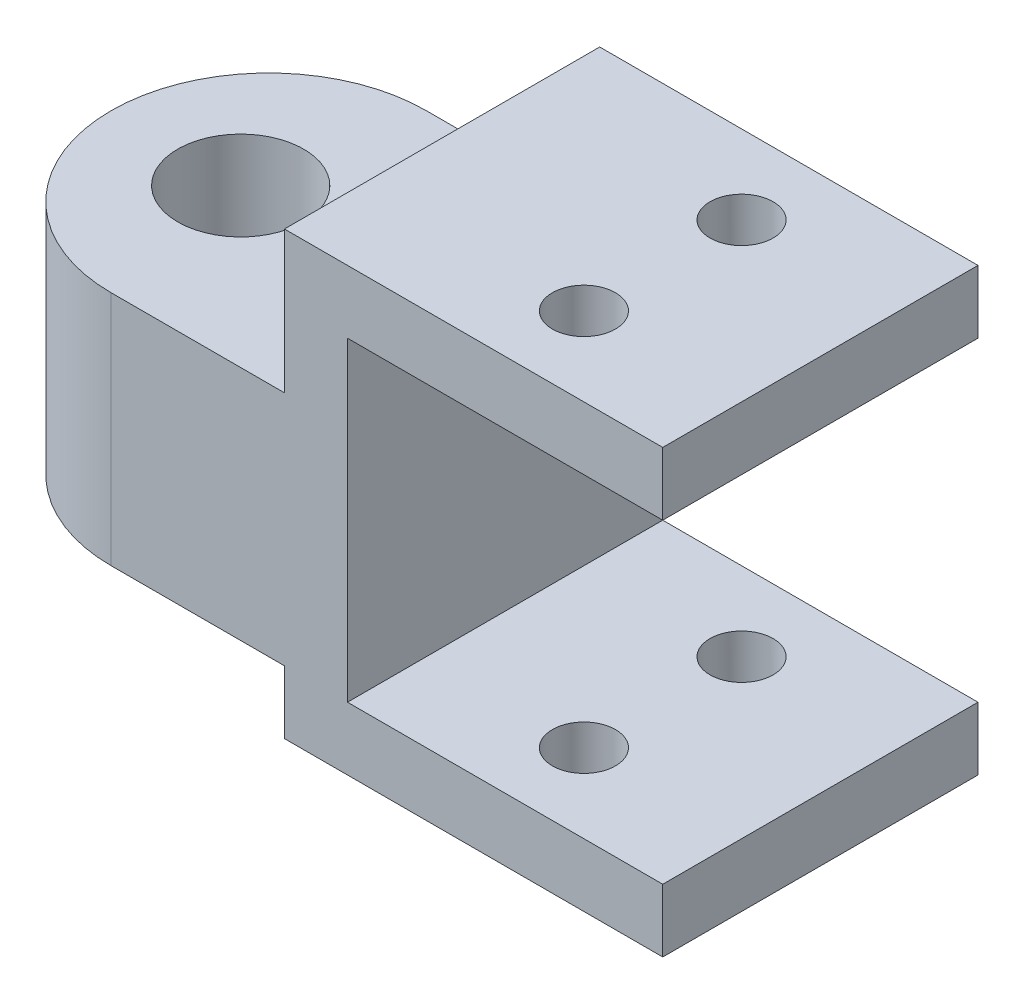
SolidWorks part; units mm, degrees
ref_plane "Front Plane" through (0, 0, 0) normal (0, 0, 1) x (1, 0, 0)
ref_plane "Top Plane" through (0, 0, 0) normal (0, 1, 0) x (1, 0, 0)
ref_plane "Right Plane" through (0, 0, 0) normal (1, 0, 0) x (0, 0, -1)
sketch "Sketch1" plane through (0, 0, 0) normal (0, 0, 1) x (1, 0, 0)
  line L1 (10, -10) -> (-10, -10) construction
  line L2 (10, -10) -> (10, 10) construction
  line L3 (10, 10) -> (-10, 10) construction
  line L4 (-10, -10) -> (-10, 10) construction
  line L5 (10, -10) -> (-10, 10) construction
  line L6 (10, 10) -> (-10, -10) construction
  line L7 (-35, 5) -> (-10, 5)
  line L8 (-35, 5) -> (-35, -10)
  line L9 (-35, -10) -> (-10, -10)
  line L10 (-10, 5) -> (-10, -10)
  line L11 (10, 10) -> (-10, 10)
  line L12 (10, 10) -> (10, 14)
  line L13 (10, 14) -> (-10, 14)
  line L14 (-10, 10) -> (-10, 14)
  line L15 (-10, 14) -> (-14, 14)
  line L16 (-10, 14) -> (-10, 5)
  line L17 (-10, 5) -> (-14, 5)
  line L18 (-14, 14) -> (-14, 5)
  line L19 (-14, -10) -> (10, -10)
  line L20 (-14, -10) -> (-14, -14)
  line L21 (-14, -14) -> (10, -14)
  line L22 (10, -10) -> (10, -14)
  point P0 (0, 0)
  dimension "D1" = 20
  dimension "D2" = 20
  dimension "D3" = 4
  dimension "D4" = 15
  dimension "D5" = 25
extrude "Boss-Extrude1" add sketch "Sketch1" along normal blind 20 contours L10 L7 L8 L9 | L15 L18 L7 L16 L14 | L14 L11 L12 L13 | L22 L19 L9 L20 L21 region at (-22.5, -2.5, 0) region at (-12, 9.5, 0) region at (-2, -12, 0) region at (0, 12, 0)
sketch "Sketch2" plane through (0, 5, 0) normal (0, 1, 0) x (1, 0, 0)
  line L0 (-10, -20) -> (-10, 0) construction
  line L1 (-35, -20) -> (-14, -20) construction
  circle A0 centre (-26.775, -10) radius 4
  dimension "D1" = 8
  dimension "D2" = 16.775
  dimension "D3" = 10
extrude "Cut-Extrude2" cut sketch "Sketch2" against normal through all contours A0
sketch "Sketch3" plane through (0, 5, 0) normal (0, 1, 0) x (1, 0, 0)
  line L0 (0, 0) -> (0, -20) construction
  line L1 (10, -20) -> (-14, -20) construction
  line L2 (10, 0) -> (-14, 0) construction
  circle A0 centre (0, -5) radius 2
  circle A1 centre (0, -15) radius 2
  dimension "D1" = 4
  dimension "D2" = 5
  dimension "D3" = 5
extrude "Cut-Extrude3" cut sketch "Sketch3" against normal through all both and the other way through all
fillet "Fillet4" radius 10 2 edges at (-35, -2.5, 0) (-35, -2.5, 20)
